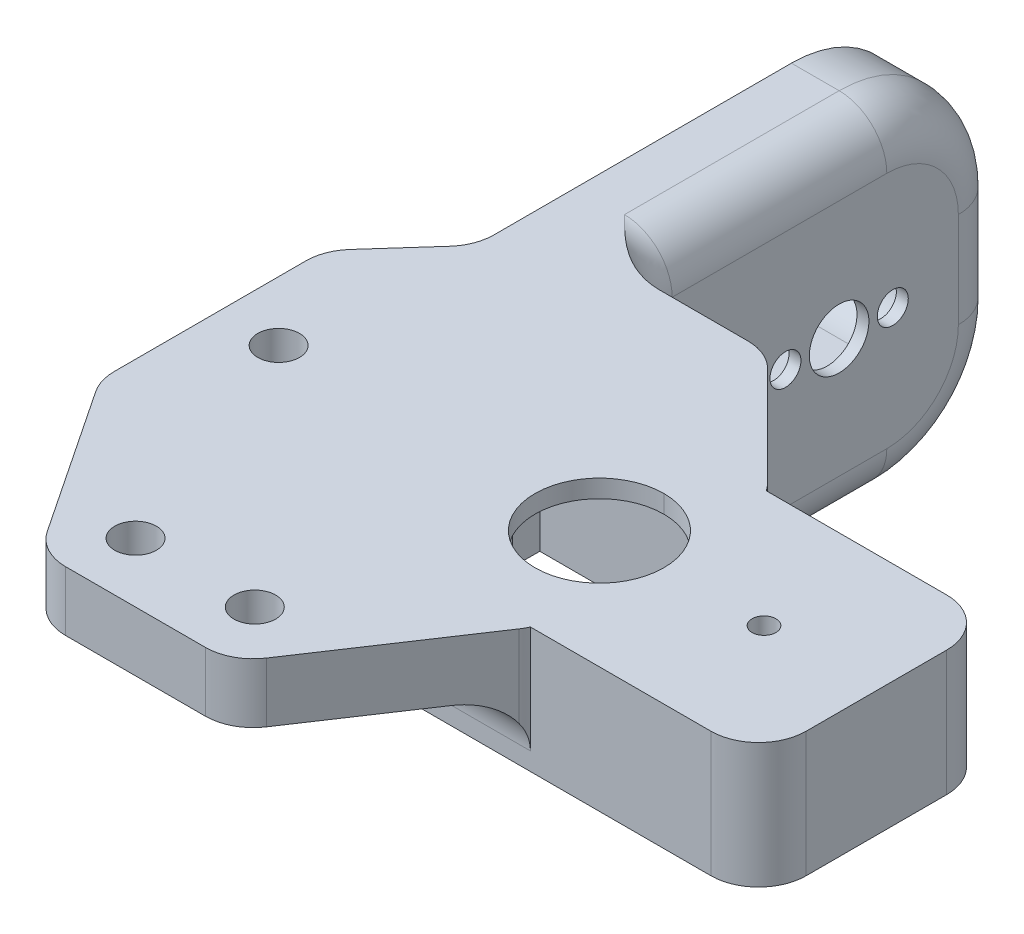
SolidWorks part; units mm, degrees
ref_plane "Front Plane" through (0, 0, 0) normal (0, 0, 1) x (1, 0, 0)
ref_plane "Top Plane" through (0, 0, 0) normal (0, 1, 0) x (1, 0, 0)
ref_plane "Right Plane" through (0, 0, 0) normal (1, 0, 0) x (0, 0, -1)
sketch "Sketch2" plane through (0, 0, 0) normal (0, 1, 0) x (1, 0, 0)
  line L0 (0, 33.8197) -> (10, 45)
  line L1 (0, 0) -> (60, 0)
  line L2 (0, 0) -> (0, 45)
  line L3 (0, 45) -> (60, 45)
  line L4 (60, 0) -> (60, 45)
  line L5 (0, 15) -> (10, 0)
  line L6 (60, 15) -> (36, 15)
  line L7 (36, 15) -> (26, 0)
  line L8 (26, 45) -> (36, 35)
  line L9 (36, 35) -> (60, 35)
  line L10 (0, 25) -> (60, 25) construction
  line L11 (37.3, 30.4) -> (37.3, 19.6)
  line L12 (44.5, 30.4) -> (26.5, 30.4)
  line L13 (44.5, 30.4) -> (44.5, 19.6)
  line L14 (44.5, 19.6) -> (26.5, 19.6)
  line L15 (26.5, 30.4) -> (26.5, 19.6)
  line L16 (44.5, 30.4) -> (26.5, 19.6) construction
  line L17 (44.5, 19.6) -> (26.5, 30.4) construction
  circle A0 centre (5, 25) radius 1.75
  circle A1 centre (13, 5) radius 1.75
  circle A2 centre (23, 5) radius 1.75
  point P17 (35.5, 25)
  dimension "D13" = 3.5
  dimension "D1" = 45
  dimension "D2" = 60
  dimension "D3" = 15
  dimension "D4" = 10
  dimension "D5" = 15
  dimension "D6" = 10
  dimension "D7" = 16
  dimension "D8" = 10
  dimension "D9" = 16
  dimension "D10" = 10
  dimension "D11" = 20
  dimension "D12" = 10
  dimension "D14" = 10
  dimension "D15" = 5
  dimension "D16" = 3
  dimension "D17" = 5
  dimension "D18" = 10
  dimension "D19" = 18
  dimension "D20" = 4.6
  dimension "D21" = 15.5
  dimension "D22" = 10.8
extrude "Boss-Extrude1" add sketch "Sketch2" along normal blind 5 contours L9 L8 L3 L0 L2 L5 L1 L7 L6 L4 A2 A1 A0 L15 L12 L13 L14 | L14 L13 L12 L11 region at (24.916, 0, -23.5142) region at (40.9, 0, -25)
fillet "Fillet1" 2 edges at (37.3, 2.5, -19.6) (37.3, 2.5, -30.4) type full round first side face at (31.9, 2.5, -19.6) second side face at (31.9, 2.5, -30.4) middle face at (37.3, 2.5, -25)
fillet "Fillet2" 2 edges at (26.5, 2.5, -19.6) (26.5, 2.5, -30.4) type full round first side face at (29.2, 2.5, -19.6) second side face at (29.2, 2.5, -30.4) middle face at (26.5, 2.5, -25)
fillet "Fillet3" 2 edges at (60, 2.5, -35) (60, 2.5, -15) type full round first side face at (48, 2.5, -35) second side face at (48, 2.5, -15) middle face at (60, 2.5, -25)
sketch "Sketch3" plane through (0, 0, 0) normal (0, -1, 0) x (1, 0, 0)
  line L5 (14.4, -15.1087) -> (49.4, -15.1087)
  line L6 (14.4, -15.1087) -> (14.4, -34.8913)
  line L11 (14.4, -34.8913) -> (49.4, -34.8913)
  line L12 (49.4, -15.1087) -> (49.4, -34.8913)
  line L13 (14.4, -15.1087) -> (49.4, -34.8913) construction
  line L14 (14.4, -34.8913) -> (49.4, -15.1087) construction
  line L15 (43.4, -18.5) -> (20.4, -18.5)
  line L16 (43.4, -18.5) -> (43.4, -31.5)
  line L17 (43.4, -31.5) -> (20.4, -31.5)
  line L18 (20.4, -18.5) -> (20.4, -31.5)
  line L19 (43.4, -18.5) -> (20.4, -31.5) construction
  line L20 (43.4, -31.5) -> (20.4, -18.5) construction
  circle A1 centre (31.9, -25) radius 6.5
  point P0 (31.9, -25)
  point P5 (31.9, -25)
  line M12 (36, -35) -> (50, -35)
  line M14 (50, -15) -> (36, -15)
  line M15 (36, -15) -> (26, 0)
  line M21 (26, -45) -> (36, -35)
  arc M27 (50, -35) -> (50, -15) centre (50, -25) ccw
  dimension "D1" = 6
  dimension "D3" = 13
  dimension "D2" = 23
  dimension "D4" = 13
extrude "Boss-Extrude2" add sketch "Sketch3" along normal blind 5.5 contours L12 L5 L6 L11 L18 L15 L16 L17 M27 M14 M15 M21 M12 region at (31.9, 0, -15.5107)
sketch "Sketch4" plane through (0, 0, 0) normal (0, -1, 0) x (1, 0, 0)
  line L4 (43.4, -18.5) -> (20.4, -18.5)
  line L5 (20.4, -18.5) -> (20.4, -31.5)
  line L6 (20.4, -31.5) -> (43.4, -31.5)
  line L7 (43.4, -31.5) -> (43.4, -18.5)
  line L8 (43.4, -18.5) -> (20.4, -18.5)
  line L9 (20.4, -18.5) -> (20.4, -31.5)
  line L10 (20.4, -31.5) -> (43.4, -31.5)
  line L11 (43.4, -31.5) -> (43.4, -18.5)
  dimension "D1" = 0
extrude "Cut-Extrude1" cut sketch "Sketch4" against normal blind 3.5
sketch "Sketch6" plane through (0, 0, 0) normal (0, -1, 0) x (1, 0, 0)
  line L0 (50, -15) -> (49.4, -15)
  line L1 (50, -35) -> (49.4, -35)
  line L2 (36, -35) -> (50, -35) construction
  line L9 (49.4, -15.1087) -> (49.4, -34.8913) construction
  line L10 (50, -15) -> (36, -15) construction
  line L12 (49.4, -15) -> (49.4, -35)
  arc A0 (50, -35) -> (50, -15) centre (50, -25) ccw construction
  arc A1 (50, -35) -> (50, -15) centre (50, -25) ccw
extrude "Cut-Extrude2" cut sketch "Sketch6" against normal through all both and the other way through all contours L0 L12 L1 A1 body kept at (26, 0, 0)
sketch "Sketch8" plane through (0, 0, 0) normal (0, -1, 0) x (1, 0, 0)
  line L0 (49.4, -35) -> (49.4, -34.8913) construction
  line L1 (14.4, -34.8913) -> (49.4, -34.8913) construction
  line L2 (36, -35) -> (49.4, -35) construction
  line L3 (49.4, -15.1087) -> (49.4, -15) construction
  line L4 (14.4, -15.1087) -> (49.4, -15.1087) construction
  line L5 (49.4, -15) -> (36, -15) construction
  line L6 (49.4, -35) -> (49.4, -34.8913)
  line L7 (36, -34.8913) -> (49.4, -34.8913)
  line L8 (36, -35) -> (49.4, -35)
  line L9 (49.4, -15.1087) -> (49.4, -15)
  line L10 (36, -15.1087) -> (49.4, -15.1087)
  line L11 (49.4, -15) -> (36, -15)
  line L12 (36, -35) -> (36, -34.8913)
  line L13 (36, -15) -> (36, -15.1087)
extrude "Cut-Extrude3" cut sketch "Sketch8" against normal through all both and the other way through all
fillet "Fillet4" radius 4 2 edges at (49.4, -0.25, -15.1087) (49.4, -0.25, -34.8913)
sketch "Sketch10" plane through (0, 0, -45) normal (0, 0, -1) x (-1, 0, 0)
  line L1 (-14, 5) -> (-6, 5)
  line L2 (-14, 5) -> (-14, -23)
  line L3 (-14, -23) -> (-6, -23)
  line L4 (-6, 5) -> (-6, -23)
  line L5 (-10, 5) -> (-10, 0) construction
  line L6 (-10, 5) -> (-26, 5) construction
  dimension "D1" = 28
  dimension "D2" = 8
  dimension "D3" = 4
extrude "Boss-Extrude4" add sketch "Sketch10" along normal blind 32
sketch "Sketch11" plane through (14, 0, 0) normal (1, 0, 0) x (0, 0, -1)
  line L0 (77, 5) -> (45, 5) construction
  line L1 (77, 5) -> (77, -23) construction
  circle A0 centre (63, -9) radius 2.5
  dimension "D1" = 14
  dimension "D2" = 5
  dimension "D3" = 14
extrude "Cut-Extrude4" cut sketch "Sketch11" against normal blind 32
fillet "Fillet5" radius 10 2 edges at (10, -23, -77) (10, 5, -77)
sketch "Sketch12" plane through (0, -5.5, 0) normal (0, -1, 0) x (1, 0, 0)
  line L0 (43.4, -25) -> (20.4, -25) construction
  line L1 (43.4, -18.5) -> (43.4, -31.5) construction
  line L2 (20.4, -18.5) -> (20.4, -31.5) construction
  circle A0 centre (18.1, -25) radius 1
  circle A1 centre (45.7, -25) radius 1
  dimension "D1" = 2
  dimension "D2" = 2.3
  dimension "D3" = 27.6
extrude "Cut-Extrude5" cut sketch "Sketch12" against normal blind 32
sketch "Sketch15" plane through (6, 0, 0) normal (-1, 0, 0) x (0, 0, 1)
  line L0 (-45, -23) -> (-45, 5)
  line L1 (-45, 5) -> (-35, 5)
  line L2 (-35, 5) -> (-34.8913, -5.5)
  line L3 (-34.8913, -5.5) -> (-45, -23)
  line L4 (-34.8913, -5.5) -> (-34.8913, 0) construction
extrude "Boss-Extrude5" add sketch "Sketch15" against normal up to vertex (8 mm away) up to point (14, 0, -45)
sketch "Sketch16" plane through (6, 0, 0) normal (-1, 0, 0) x (0, 0, 1)
  line L0 (-67.5, -9) -> (-63, -9) construction
  circle A0 centre (-58.5, -9) radius 1.3
  circle A1 centre (-67.5, -9) radius 1.3
  circle A4 centre (-63, -9) radius 2.5 construction
  dimension "D1" = 2.6
  dimension "D2" = 4.5
  dimension "D3" = 9
extrude "Cut-Extrude6" cut sketch "Sketch16" against normal blind 32
sketch "Sketch17" plane through (6, 0, 0) normal (-1, 0, 0) x (0, 0, 1)
  line L1 (-56, -5.5) -> (-70, -5.5)
  line L2 (-56, -5.5) -> (-56, -12.5)
  line L3 (-56, -12.5) -> (-70, -12.5)
  line L4 (-70, -5.5) -> (-70, -12.5)
  line L5 (-56, -5.5) -> (-70, -12.5) construction
  line L6 (-56, -12.5) -> (-70, -5.5) construction
  point P0 (-63, -9)
  dimension "D1" = 14
  dimension "D2" = 7
extrude "Cut-Extrude7" cut sketch "Sketch17" against normal blind 7
fillet "Fillet6" 2 edges at (9.5, -5.5, -70) (9.5, -12.5, -70) type full round first side face at (9.5, -5.5, -63) second side face at (9.5, -12.5, -63) middle face at (9.5, -9, -70)
fillet "Fillet7" 2 edges at (9.5, -12.5, -56) (9.5, -5.5, -56) type full round first side face at (9.5, -12.5, -61.25) second side face at (9.5, -5.5, -61.25) middle face at (9.5, -9, -56)
sketch "Sketch18" plane through (6, 0, 0) normal (-1, 0, 0) x (0, 0, 1)
  line L0 (-45, -23) -> (-34.8913, -5.5) construction
  line L1 (-45, -23) -> (-34.8913, -5.5)
  line L2 (-45, -23) -> (-55, -23)
  line L4 (-55, -23) -> (-34.8913, -5.5)
  dimension "D1" = 10
extrude "Cut-Extrude8" cut sketch "Sketch18" against normal through all both and the other way through all
fillet "Fillet8" radius 8 2 edges at (10, -23, -55) (10, -5.5, -34.8913)
fillet "Fillet11" radius 4 9 edges at (14, -0.9035, -34.9389) (14, -5.1676, -35.6314) (14, -14.4796, -45.2095) (14, -22.4926, -55.1899) (14, -23, -62.4968) (14, 5, -56) (14, 2.0711, -74.0711) (14, -9, -77) (14, -20.0711, -74.0711)
fillet "Fillet9" radius 4 11 edges at (6, 0, -37.7381) (14, 0.5, -45) (26, 2.5, -45) (36, 2.5, -35) (36, 2.5, -15) (26, 2.5, 0) (10, 2.5, 0) (0, 2.5, -15) (6, 2.5, -40.5279) (0, 2.5, -33.8197) (12.8284, 3.8284, -45)
fillet "Fillet10" radius 4 3 edges at (25.2, 0, -34.8913) (14.4, 0, -25) (25.2, 0, -15.1087)
sketch "Sketch21" plane through (0, -5.5, 0) normal (0, -1, 0) x (1, 0, 0)
  line L0 (20.4, -18.5) -> (20.4, -31.5) construction
  line L1 (20.4, -18.5) -> (20.4, -31.5)
  line L2 (20.4, -18.5) -> (25.6108, -18.5)
  line L3 (43.4, -18.5) -> (20.4, -18.5) construction
  line L4 (25.6108, -18.5) -> (25.6108, -31.5)
  line L5 (43.4, -31.5) -> (20.4, -31.5) construction
  line L6 (25.6108, -31.5) -> (20.4, -31.5)
  line L7 (49.4, -19.1087) -> (49.4, -30.8913)
  line L8 (45.4, -34.8913) -> (55.1343, -34.8913)
  line L9 (55.1343, -34.8913) -> (55.1343, -15.1087)
  line L10 (55.1343, -15.1087) -> (45.4, -15.1087)
  arc A0 (22.3648, -25.55) -> (22.3648, -24.45) centre (23.2, -25) ccw construction
  circle A1 centre (23.2, -25) radius 1
  circle A2 centre (18.1, -25) radius 1 construction
  circle A3 centre (18.1, -25) radius 1
  arc A4 (51.6352, -24.45) -> (51.6352, -25.55) centre (50.8, -25) ccw construction
  circle A5 centre (50.8, -25) radius 1
  arc A6 (45.4, -34.8913) -> (49.4, -30.8913) centre (45.4, -30.8913) ccw construction
  arc A7 (49.4, -19.1087) -> (45.4, -15.1087) centre (45.4, -19.1087) ccw construction
  arc A8 (49.4, -19.1087) -> (45.4, -15.1087) centre (45.4, -19.1087) ccw
  arc A9 (45.4, -34.8913) -> (49.4, -30.8913) centre (45.4, -30.8913) ccw
  circle M1 centre (18.1, -25) radius 1
extrude "Boss-Extrude6" add sketch "Sketch21" against normal up to surface (10.5 mm away) contours M1 region at (18.1, -5.5, -25) up to face at (21.4577, 5, -29.0436)
extrude "Boss-Extrude7" add sketch "Sketch21<3>" against normal up to surface (9 mm away) contours A1 region at (23.2, -5.5, -25) up to face at (31.9, 3.5, -25)
sketch "Sketch21<3>" plane through (0, -5.5, 0) normal (0, -1, 0) x (1, 0, 0) same geometry as "Sketch21"
extrude "Boss-Extrude8" add sketch "Sketch21<4>" against normal up to surface (10.5 mm away) contours L9 L10 A8 L7 A9 L8 up to face at (21.4577, 5, -29.0436)
sketch "Sketch21<4>" plane through (0, -5.5, 0) normal (0, -1, 0) x (1, 0, 0) same geometry as "Sketch21"
fillet "Fillet12" radius 4 2 edges at (55.1343, -0.25, -15.1087) (55.1343, -0.25, -34.8913)
